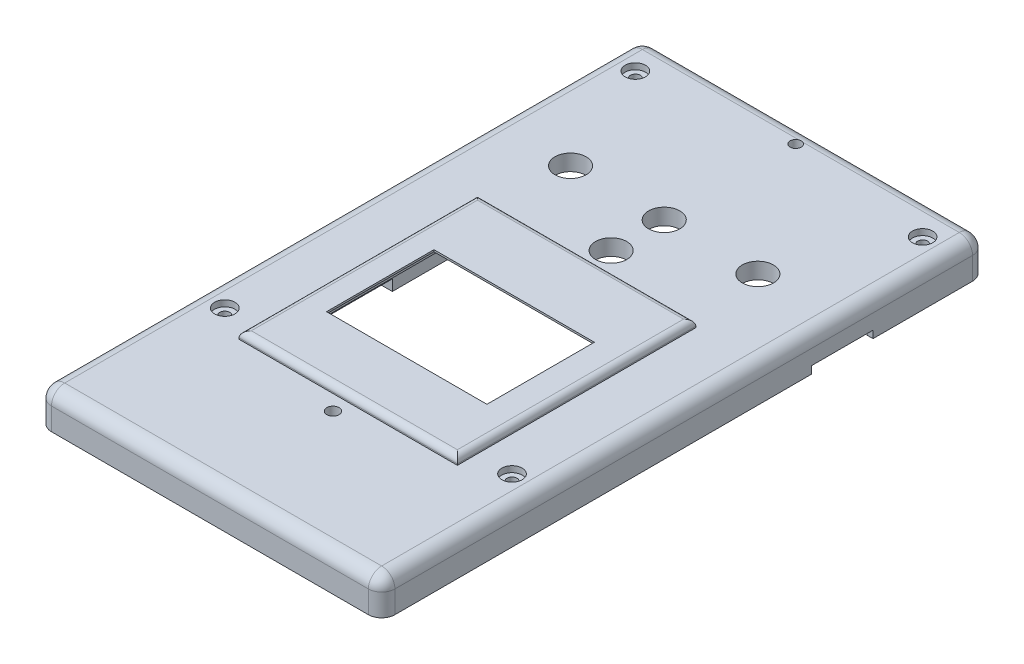
SolidWorks part; units mm, degrees
ref_plane "Face" through (0, 0, 0) normal (0, 0, 1) x (1, 0, 0)
ref_plane "Dessus" through (0, 0, 0) normal (0, 1, 0) x (1, 0, 0)
ref_plane "Droite" through (0, 0, 0) normal (1, 0, 0) x (0, 0, -1)
sketch "Sketch1" plane through (0, 0, 0) normal (0, 1, 0) x (1, 0, 0)
  line L0 (0, -49.53) -> (0, 0) construction
  line L1 (27.94, -49.53) -> (-27.94, -49.53)
  line L2 (27.94, -49.53) -> (27.94, 48.768)
  line L3 (27.94, 48.768) -> (-27.94, 48.768)
  line L4 (-27.94, -49.53) -> (-27.94, 48.768)
  point P0 (0, 0)
  dimension "D1" = 55.88
  dimension "D2" = 49.53
  dimension "D3" = 48.768
extrude "Boss-Extrude1" add sketch "Sketch1" along normal blind 4.99
fillet "Fillet1" radius 2.159 8 edges at (0, 4.99, 49.53) (27.94, 4.99, 0.381) (0, 4.99, -48.768) (-27.94, 4.99, 0.381) (-27.94, 2.495, -48.768) (27.94, 2.495, -48.768) (27.94, 2.495, 49.53) (-27.94, 2.495, 49.53)
sketch "Sketch3" plane through (0, 0, 0) normal (0, -1, 0) x (1, 0, 0)
  line L1 (21.6281, -38.862) -> (-20.4089, -38.862)
  line L2 (21.6281, -38.862) -> (21.6281, 26.576)
  line L3 (21.6281, 26.576) -> (-20.4089, 26.576)
  line L4 (-20.4089, -38.862) -> (-20.4089, 26.576)
  line L5 (21.6281, -38.862) -> (-20.4089, 26.576) construction
  line L6 (21.6281, 26.576) -> (-20.4089, -38.862) construction
  point P0 (0.6096, -6.143)
  dimension "D1" = 42.037
  dimension "D2" = 26.576
  dimension "D3" = 38.862
  dimension "D4" = 0.6096
sketch "Sketch7" plane through (0, 0, 0) normal (0, -1, 0) x (1, 0, 0)
  line L6 (-25.781, -47.752) -> (25.781, -47.752)
  line L9 (26.924, 47.371) -> (26.924, -46.609)
  line L10 (-26.924, -46.609) -> (-26.924, 47.371)
  line L11 (-25.781, 48.514) -> (25.781, 48.514)
  line L12 (26.924, 47.371) -> (26.924, -46.609)
  line L13 (-26.924, -46.609) -> (-26.924, 47.371)
  line L14 (-25.781, 48.514) -> (25.781, 48.514)
  arc A9 (25.781, -47.752) -> (26.924, -46.609) centre (25.781, -46.609) ccw
  arc A16 (25.781, -47.752) -> (26.924, -46.609) centre (25.781, -46.609) ccw
  arc A17 (-26.924, -46.609) -> (-25.781, -47.752) centre (-25.781, -46.609) ccw
  arc A18 (-26.924, -46.609) -> (-25.781, -47.752) centre (-25.781, -46.609) ccw
  arc A19 (-25.781, 48.514) -> (-26.924, 47.371) centre (-25.781, 47.371) ccw
  arc A20 (-25.781, 48.514) -> (-26.924, 47.371) centre (-25.781, 47.371) ccw
  arc A21 (26.924, 47.371) -> (25.781, 48.514) centre (25.781, 47.371) ccw
  arc A22 (26.924, 47.371) -> (25.781, 48.514) centre (25.781, 47.371) ccw
  dimension "D1" = 1.016
  dimension "D2" = 1.016
extrude "Cut-Extrude4" cut sketch "Sketch7" against normal blind 0.5874
sketch "Sketch8" plane through (0, 0, 0) normal (0, -1, 0) x (1, 0, 0)
  line L0 (27.94, 47.371) -> (27.94, -46.609) construction
  line L2 (26.924, -46.609) -> (26.924, 47.371) construction
  line L3 (-25.781, -47.752) -> (25.781, -47.752) construction
  line L4 (26.924, -46.609) -> (26.924, -40.386)
  line L5 (21.717, -47.752) -> (25.781, -47.752)
  line L6 (21.717, -47.752) -> (21.717, -40.386)
  line L7 (21.717, -40.386) -> (26.924, -40.386)
  circle A0 centre (23.4188, -43.006) radius 0.889
  arc A1 (25.781, -47.752) -> (26.924, -46.609) centre (25.781, -46.609) ccw construction
  arc A2 (25.781, -47.752) -> (26.924, -46.609) centre (25.781, -46.609) ccw
  dimension "D3" = 1.778
  dimension "D1" = 4.5212
  dimension "D2" = 43.006
  dimension "D4" = 6.223
  dimension "D5" = 40.386
sketch "Sketch9" plane through (0, 0, 0) normal (0, -1, 0) x (1, 0, 0)
  line L0 (-26.924, 47.371) -> (-26.924, -46.609) construction
  line L1 (-25.781, -47.752) -> (25.781, -47.752) construction
  line L2 (-26.924, -40.005) -> (-26.924, -46.609)
  line L3 (-25.781, -47.752) -> (-20.447, -47.752)
  line L4 (-20.447, -47.752) -> (-20.447, -40.005)
  line L5 (-20.447, -40.005) -> (-26.924, -40.005)
  line L6 (-27.94, -46.609) -> (-27.94, 47.371) construction
  arc A0 (-26.924, -46.609) -> (-25.781, -47.752) centre (-25.781, -46.609) ccw construction
  arc A1 (-26.924, -46.609) -> (-25.781, -47.752) centre (-25.781, -46.609) ccw
  circle A2 centre (-23.3172, -43.006) radius 0.889
  dimension "D5" = 1.778
  dimension "D1" = 7.493
  dimension "D2" = 43.006
  dimension "D3" = 3.6068
  dimension "D4" = 40.005
sketch "Sketch10" plane through (0, 0, 0) normal (0, -1, 0) x (1, 0, 0)
  line L0 (-27.94, -46.609) -> (-27.94, 47.371) construction
  line L1 (-26.924, 47.371) -> (-26.924, -46.609) construction
  line L2 (-26.924, 17.78) -> (-20.447, 17.78)
  line L3 (-26.924, 17.78) -> (-26.924, 26.67)
  line L4 (-26.924, 26.67) -> (-20.447, 26.67)
  line L5 (-20.447, 17.78) -> (-20.447, 26.67)
  circle A0 centre (-23.3172, 23.796) radius 0.889
  dimension "D6" = 1.778
  dimension "D1" = 4.6228
  dimension "D2" = 23.796
  dimension "D3" = 6.477
  dimension "D4" = 26.67
  dimension "D5" = 17.78
sketch "Sketch11" plane through (0, 0, 0) normal (0, -1, 0) x (1, 0, 0)
  line L0 (26.924, -46.609) -> (26.924, 47.371) construction
  line L1 (26.924, 27.686) -> (21.7502, 27.686)
  line L2 (26.924, 27.686) -> (26.924, 20.32)
  line L3 (26.924, 20.32) -> (21.7502, 20.32)
  line L4 (21.7502, 27.686) -> (21.7502, 20.32)
  circle A0 centre (23.4188, 23.796) radius 0.889
  dimension "D6" = 1.778
  dimension "D1" = 23.796
  dimension "D2" = 23.4188
  dimension "D3" = 27.686
  dimension "D4" = 20.32
  dimension "D5" = 21.7502
sketch "Sketch12" plane through (0, 0.5874, 0) normal (0, -1, 0) x (1, 0, 0)
  line L0 (26.924, -38.1) -> (19.812, -38.1)
  line L1 (-26.924, 27.94) -> (-16.28, 27.94)
  line L3 (-26.924, 13.7274) -> (-16.28, 13.7274)
  line L4 (26.924, -46.609) -> (26.924, 47.371)
  line L5 (25.781, 48.514) -> (-25.781, 48.514)
  line L6 (-26.924, 47.371) -> (-26.924, -46.609)
  line L7 (-25.781, -47.752) -> (25.781, -47.752)
  line L8 (26.924, -38.1) -> (26.924, -17.145)
  line L9 (25.781, 48.514) -> (8.5725, 48.514)
  line L10 (-26.924, 47.371) -> (-26.924, 27.94)
  line L11 (-19.812, -47.752) -> (19.812, -47.752)
  line L12 (-16.28, 27.94) -> (-16.28, 13.7274)
  line L13 (26.924, 27.94) -> (19.812, 27.94)
  line L17 (19.812, -38.1) -> (19.812, -47.752)
  line L18 (-26.924, -38.1) -> (-19.812, -38.1)
  line L19 (-19.812, -38.1) -> (-19.812, -47.752)
  line L20 (-26.924, 3.429) -> (-16.28, 3.429)
  line L21 (-16.28, 3.429) -> (-16.28, -17.145)
  line L22 (-16.28, -17.145) -> (-26.924, -17.145)
  line L25 (19.812, -17.145) -> (26.924, -17.145)
  line L26 (0, 44.704) -> (0, 0) construction
  line L28 (8.5725, 48.514) -> (8.5725, 44.704)
  line L29 (8.5725, 44.704) -> (-8.5725, 44.704)
  line L30 (-8.5725, 48.514) -> (-8.5725, 44.704)
  line L31 (0, 0) -> (0, -47.752) construction
  line L36 (-8.5725, 48.514) -> (-25.781, 48.514)
  line L37 (26.924, 27.94) -> (26.924, 47.371)
  line L38 (-26.924, 13.7274) -> (-26.924, 3.429)
  line L39 (-26.924, -17.145) -> (-26.924, -38.1)
  line L40 (26.924, -3.275) -> (26.924, 12.725)
  line L41 (19.812, -17.145) -> (19.812, -11.275)
  line L42 (19.812, -11.275) -> (22.346, -11.275)
  line L43 (22.346, -11.275) -> (22.346, -3.275)
  line L44 (22.346, -3.275) -> (26.924, -3.275)
  line L45 (19.812, 27.94) -> (19.812, 20.725)
  line L46 (19.812, 20.725) -> (22.346, 20.725)
  line L47 (22.346, 20.725) -> (22.346, 12.725)
  line L48 (22.346, 12.725) -> (26.924, 12.725)
  arc A4 (25.781, -47.752) -> (26.924, -46.609) centre (25.781, -46.609) ccw
  arc A5 (26.924, 47.371) -> (25.781, 48.514) centre (25.781, 47.371) ccw
  arc A6 (-25.781, 48.514) -> (-26.924, 47.371) centre (-25.781, 47.371) ccw
  arc A7 (-26.924, -46.609) -> (-25.781, -47.752) centre (-25.781, -46.609) ccw
  arc A9 (26.924, 47.371) -> (25.781, 48.514) centre (25.781, 47.371) ccw
  arc A10 (-25.781, 48.514) -> (-26.924, 47.371) centre (-25.781, 47.371) ccw
  line M33 (26.924, -46.609) -> (26.924, 47.371)
  arc M34 (26.924, 47.371) -> (25.781, 48.514) centre (25.781, 47.371) ccw
  line M35 (25.781, 48.514) -> (-25.781, 48.514)
  arc M36 (-25.781, 48.514) -> (-26.924, 47.371) centre (-25.781, 47.371) ccw
  line M37 (-26.924, 47.371) -> (-26.924, -46.609)
  line M39 (-25.781, -47.752) -> (25.781, -47.752)
  dimension "D2" = 12.725
  dimension "D3" = 17.145
  dimension "D4" = 3.81
  dimension "D5" = 27.94
  dimension "D6" = 14.2126
  dimension "D7" = 3.429
  dimension "D8" = 17.145
  dimension "D9" = 38.1
  dimension "D10" = 39.624
  dimension "D11" = 16.28
  dimension "D12" = 4.578
  dimension "D13" = 32
  dimension "D14" = 20.725
  dimension "D15" = 16
  dimension "D1" = 0
extrude "Cut-Extrude5" cut sketch "Sketch12" against normal blind 1.778 contours L17 L0 L25 L41 L48 L13 L28 L29 L30 L1 L12 L3 L20 L21 L22 L18 L19 M39 M33 M34 M35 M36 M37 region at (0.9045, 0.5874, 0.4828)
fillet "Fillet4" radius 1.016 11 edges at (26.924, 2.3654, 37.6555) (26.5892, 2.3654, 48.1792) (-26.924, 2.3654, 37.6555) (-26.5892, 2.3654, 48.1792) (0, 2.3654, -47.752) (-26.924, 2.3654, 8.5782) (-26.924, 2.3654, -27.6225) (26.924, 2.3654, -27.6225) (26.924, 2.3654, 4.725) (17.1767, 2.3654, 48.514) (-17.1767, 2.3654, 48.514)
hole_wizard "Chambrage pour vis à tête ronde à 6 pans creux #11" positions "Sketch13" profile "Sketch14" counterbore size "#1" standard "Ansi Inch"
sketch "Sketch13" plane through (0, 4.99, 0) normal (0, 1, 0) x (1, 0, 0)
  point P0 (-23.3172, -23.796)
  point P3 (23.4188, -23.796)
  point P6 (23.4188, 43.006)
  point P9 (-23.3172, 43.006)
sketch "Sketch14" plane through (-23.3172, 4.99, 23.796) normal (1, 0, 0) x (0, 0, 1)
  line L0 (0, 0) -> (0, 6.4807)
  line L1 (0, 6.4807) -> (0.8001, 6)
  line L2 (0.8001, 6) -> (0.8001, 0.9906)
  line L3 (0.8001, 0.9906) -> (1.651, 0.9906)
  line L4 (1.651, 0.9906) -> (1.651, 0)
  line L5 (1.651, 0) -> (0, 0)
  line L10 (0, 6.4807) -> (-0.8001, 6) construction
  line L11 (0, -6.35) -> (0, 107.95) construction
  dimension "Diamètre du perçage" = 1.6002
  dimension "Profondeur du perçage" = 6
  dimension "Diamètre du chambrage" = 3.302
  dimension "Profondeur du chambrage" = 0.9906
  dimension "Angle de pointe" = 118
sketch "Sketch15" plane through (0, 2.3654, 0) normal (0, -1, 0) x (1, 0, 0)
  line L0 (0, 0) -> (0, -15.748) construction
  line L1 (0, -15.748) -> (0, -24.384) construction
  line L2 (0, -24.384) -> (-15.24, -24.384) construction
  line L3 (0, -24.384) -> (15.24, -24.384) construction
  circle A0 centre (0, -24.384) radius 2.54
  circle A1 centre (-15.24, -24.384) radius 2.54
  circle A2 centre (15.24, -24.384) radius 2.54
  circle A3 centre (0, -15.748) radius 2.54
  dimension "D4" = 5.08
  dimension "D1" = 24.384
  dimension "D2" = 15.748
  dimension "D3" = 30.48
extrude "Cut-Extrude6" cut sketch "Sketch15" against normal through all
sketch "Sketch16" plane through (0, 0.5874, 0) normal (0, 1, 0) x (1, 0, 0)
  line L0 (-25.781, -48.514) -> (-8.5725, -48.514) construction
  line L1 (16.424, -25.764) -> (-16.424, -25.764)
  line L2 (16.424, -25.764) -> (16.424, 11.236)
  line L3 (16.424, 11.236) -> (-16.424, 11.236)
  line L4 (-16.424, -25.764) -> (-16.424, 11.236)
  line L5 (26.924, 46.609) -> (26.924, -47.371) construction
  point P9 (0, 11.236)
  dimension "D1" = 22.75
  dimension "D2" = 10.5
  dimension "D3" = 37
extrude "Cut-Extrude7" cut sketch "Sketch16" along normal blind 4.2
sketch "Sketch17" plane through (0, 0, 0) normal (0, -1, 0) x (1, 0, 0)
  line L0 (-25.781, -47.752) -> (25.781, -47.752) construction
  line L1 (26.924, -46.609) -> (26.924, 47.371) construction
  line L2 (25.781, 48.514) -> (-25.781, 48.514) construction
  line L3 (-26.924, 47.371) -> (-26.924, -46.609) construction
  line L4 (-27.94, 47.371) -> (-27.94, -46.609)
  line L5 (-25.781, -48.768) -> (25.781, -48.768)
  line L6 (27.94, -46.609) -> (27.94, 47.371)
  line L7 (25.781, 49.53) -> (-25.781, 49.53)
  line L8 (-27.94, 47.371) -> (-27.94, -46.609)
  line L9 (-25.781, -48.768) -> (25.781, -48.768)
  line L10 (27.94, -46.609) -> (27.94, 47.371)
  line L11 (25.781, 49.53) -> (-25.781, 49.53)
  line L12 (-25.781, -47.752) -> (25.781, -47.752)
  line L13 (26.924, -46.609) -> (26.924, 47.371)
  line L14 (25.781, 48.514) -> (-25.781, 48.514)
  line L15 (-26.924, 47.371) -> (-26.924, -46.609)
  arc A0 (-26.924, -46.609) -> (-25.781, -47.752) centre (-25.781, -46.609) ccw construction
  arc A1 (25.781, -47.752) -> (26.924, -46.609) centre (25.781, -46.609) ccw construction
  arc A2 (26.924, 47.371) -> (25.781, 48.514) centre (25.781, 47.371) ccw construction
  arc A3 (-25.781, 48.514) -> (-26.924, 47.371) centre (-25.781, 47.371) ccw construction
  arc A4 (-27.94, -46.609) -> (-25.781, -48.768) centre (-25.781, -46.609) ccw
  arc A5 (25.781, -48.768) -> (27.94, -46.609) centre (25.781, -46.609) ccw
  arc A6 (27.94, 47.371) -> (25.781, 49.53) centre (25.781, 47.371) ccw
  arc A7 (-25.781, 49.53) -> (-27.94, 47.371) centre (-25.781, 47.371) ccw
  arc A8 (-27.94, -46.609) -> (-25.781, -48.768) centre (-25.781, -46.609) ccw
  arc A9 (25.781, -48.768) -> (27.94, -46.609) centre (25.781, -46.609) ccw
  arc A10 (27.94, 47.371) -> (25.781, 49.53) centre (25.781, 47.371) ccw
  arc A11 (-25.781, 49.53) -> (-27.94, 47.371) centre (-25.781, 47.371) ccw
  arc A12 (-26.924, -46.609) -> (-25.781, -47.752) centre (-25.781, -46.609) ccw
  arc A13 (25.781, -47.752) -> (26.924, -46.609) centre (25.781, -46.609) ccw
  arc A14 (26.924, 47.371) -> (25.781, 48.514) centre (25.781, 47.371) ccw
  arc A15 (-25.781, 48.514) -> (-26.924, 47.371) centre (-25.781, 47.371) ccw
  dimension "D1" = 0
extrude "Boss-Extrude2" add sketch "Sketch17" along normal blind 0.8
sketch "Esquisse19" plane through (0, 4.99, 0) normal (0, 1, 0) x (1, 0, 0)
  line L0 (-25.781, 48.768) -> (25.781, 48.768) construction
  line L1 (17.765, 11.768) -> (-17.765, 11.768)
  line L2 (17.765, 11.768) -> (17.765, -27.03)
  line L3 (17.765, -27.03) -> (-17.765, -27.03)
  line L4 (-17.765, 11.768) -> (-17.765, -27.03)
  line L5 (-27.94, -47.371) -> (-27.94, 46.609) construction
  line L6 (27.94, 46.609) -> (27.94, -47.371) construction
  line L7 (25.781, -49.53) -> (-25.781, -49.53) construction
  dimension "D1" = 37
  dimension "D2" = 10.175
  dimension "D3" = 10.175
  dimension "D4" = 22.5
extrude "Boss.-Extru.2" add sketch "Esquisse19" along normal blind 1.2
sketch "Esquisse1" plane through (0, 4.99, 0) normal (0, 1, 0) x (1, 0, 0)
  line L0 (25.781, -48.514) -> (-25.781, -48.514) construction
  circle A0 centre (0, -29.514) radius 1
  dimension "D1" = 19
  dimension "D2" = 2
extrude "Enlèv. mat.-Extru.1" cut sketch "Esquisse1" against normal through all
sketch "Esquisse5" plane through (27.94, 0, 0) normal (1, 0, 0) x (0, 0, -1)
  line L0 (46.609, -0.8) -> (-47.371, -0.8) construction
  line L1 (30.418, -0.8) -> (20.418, -0.8)
  line L2 (30.418, -0.8) -> (30.418, 0.4)
  line L3 (30.418, 0.4) -> (20.418, 0.4)
  line L4 (20.418, -0.8) -> (20.418, 0.4)
  line L5 (48.768, 2.831) -> (48.768, -0.8) construction
  dimension "D1" = 18.35
  dimension "D2" = 10
  dimension "D3" = 1.2
extrude "Enlèv. mat.-Extru.3" cut sketch "Esquisse5" against normal blind 2
sketch "Esquisse13" plane through (0, 4.7874, 0) normal (0, -1, 0) x (1, 0, 0)
  line L0 (16.424, -11.236) -> (16.424, 25.764) construction
  line L1 (-14.124, 23.914) -> (13.624, 23.914)
  line L2 (-14.124, 23.914) -> (-14.124, -7.236)
  line L3 (-14.124, -7.236) -> (13.624, -7.236)
  line L4 (13.624, 23.914) -> (13.624, -7.236)
  line L5 (-16.424, 25.764) -> (16.424, 25.764) construction
  line L8 (-16.28, -11.236) -> (16.424, -11.236) construction
  line L9 (-16.424, -11.236) -> (-16.424, 25.764) construction
  dimension "D1" = 2.8
  dimension "D2" = 2.3
  dimension "D3" = 1.85
  dimension "D4" = 4
extrude "Enlèv. mat.-Extru.6" cut sketch "Esquisse13" against normal blind 1.1
sketch "Esquisse14" plane through (0, 4.99, 0) normal (0, 1, 0) x (1, 0, 0)
  line L4 (25.781, -47.371) -> (25.781, 46.609) construction
  circle A0 centre (0, 45.768) radius 0.9
  dimension "D1" = 1.8
  dimension "D2" = 25.781
extrude "Enlèv. mat.-Extru.7" cut sketch "Esquisse14" against normal blind 10
sketch "Esquisse15" plane through (0, 0, -48.768) normal (0, 0, -1) x (-1, 0, 0)
  line L0 (25.781, -0.8) -> (-25.781, -0.8) construction
  line L1 (19.85, -0.8) -> (7.91, -0.8)
  line L2 (19.85, -0.8) -> (19.85, -0.7)
  line L3 (19.85, -0.7) -> (7.91, -0.7)
  line L4 (7.91, -0.8) -> (7.91, -0.7)
  line L5 (27.94, 2.831) -> (27.94, -0.8) construction
  dimension "D1" = 8.09
  dimension "D2" = 11.94
  dimension "D3" = 0.1
extrude "Enlèv. mat.-Extru.8" cut sketch "Esquisse15" against normal up to next
chamfer "Chanfrein1" distance 1 angle 50 1 edges at (-13.88, -0.7, -48.768) first distance on face at (-6.94, 0.1327, -48.768)
sketch "Esquisse16" plane through (0, 0, -48.768) normal (0, 0, -1) x (-1, 0, 0)
  line L0 (7.91, -0.8) -> (-25.781, -0.8) construction
  line L1 (-18.76, -0.8) -> (-6.95, -0.8)
  line L2 (-18.76, -0.8) -> (-18.76, -0.3)
  line L3 (-18.76, -0.3) -> (-6.95, -0.3)
  line L4 (-6.95, -0.8) -> (-6.95, -0.3)
  line L5 (-27.94, -0.8) -> (-27.94, 2.831) construction
  dimension "D1" = 20.99
  dimension "D2" = 9.18
  dimension "D3" = 0.5
extrude "Enlèv. mat.-Extru.9" cut sketch "Esquisse16" against normal up to next
sketch "Esquisse17" plane through (0, 0, -48.768) normal (0, 0, -1) x (-1, 0, 0)
  line L0 (7.91, -0.8) -> (-6.95, -0.8) construction
  line L1 (-4.5, -0.8) -> (4.5, -0.8)
  line L2 (-4.5, -0.8) -> (-4.5, 0)
  line L3 (-4.5, 0) -> (4.5, 0)
  line L4 (4.5, -0.8) -> (4.5, 0)
  line L5 (-27.94, -0.8) -> (-27.94, 2.831) construction
  line L6 (27.94, 2.831) -> (27.94, -0.8) construction
  dimension "D1" = 23.44
  dimension "D2" = 23.44
  dimension "D3" = 0.8
extrude "Enlèv. mat.-Extru.10" cut sketch "Esquisse17" against normal blind 10
sketch "Esquisse18" plane through (0, 0, -48.768) normal (0, 0, -1) x (-1, 0, 0)
  line L0 (-4.5, -0.8) -> (-5, -0.8)
  line L1 (-4.5, -0.8) -> (-6.95, -0.8) construction
  line L2 (-5, -0.8) -> (-5, 0.5)
  line L3 (-5, 0.5) -> (5, 0.5)
  line L4 (5, 0.5) -> (5, -0.8)
  line L5 (7.91, -0.8) -> (4.5, -0.8) construction
  line L6 (5, -0.8) -> (4.5, -0.8)
  line L7 (4.5, -0.8) -> (4.5, 0)
  line L8 (4.5, 0) -> (-4.5, 0)
  line L9 (-4.5, 0) -> (-4.5, -0.8)
  dimension "D1" = 0.5
  dimension "D2" = 0.5
  dimension "D3" = 0.5
extrude "Boss.-Extru.1" add sketch "Esquisse18" along normal blind 1.1
fillet "Congé1" radius 0.2 3 edges at (5, -0.15, -49.868) (0, 0.5, -49.868) (-5, -0.15, -49.868)
sketch "Esquisse12" plane through (0, 4.7874, 0) normal (0, 1, 0) x (1, 0, 0)
  line L1 (-13.334, 0.256) -> (12.764, 0.256)
  line L2 (-13.334, 0.256) -> (-13.334, -17.224)
  line L3 (-13.334, -17.224) -> (12.764, -17.224)
  line L4 (12.764, 0.256) -> (12.764, -17.224)
  line L8 (-14.124, -23.914) -> (-14.124, 7.236) construction
  line L9 (-14.124, 7.236) -> (13.624, 7.236) construction
  line L10 (13.624, 7.236) -> (13.624, -23.914) construction
  line L11 (13.624, -23.914) -> (-14.124, -23.914) construction
  dimension "D1" = 0.79
  dimension "D2" = 6.98
  dimension "D3" = 6.69
  dimension "D4" = 0.86
extrude "Enlèv. mat.-Extru.5" cut sketch "Esquisse12" along normal blind 22
fillet "Congé2" radius 1 4 edges at (0, 6.19, 27.03) (-17.765, 6.19, 7.631) (0, 6.19, -11.768) (17.765, 6.19, 7.631)
